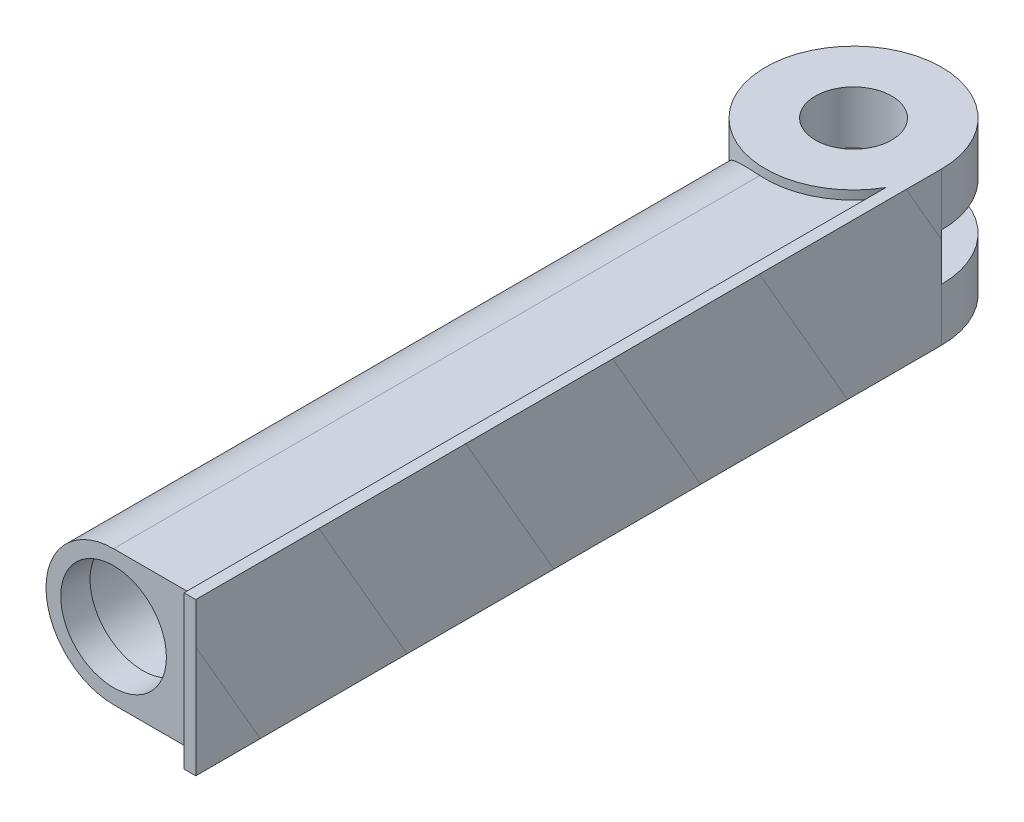
SolidWorks part; units mm, degrees
ref_plane "Front Plane" through (0, 0, 0) normal (0, 0, 1) x (1, 0, 0)
ref_plane "Top Plane" through (0, 0, 0) normal (0, 1, 0) x (1, 0, 0)
ref_plane "Right Plane" through (0, 0, 0) normal (1, 0, 0) x (0, 0, -1)
sketch "Sketch1" plane through (0, 0, 0) normal (0, 1, 0) x (1, 0, 0)
  circle A0 centre (0, 0) radius 30
  dimension "D1" = 60
extrude "Boss-Extrude1" add sketch "Sketch1" along normal mid plane 52
sketch "Sketch3" plane through (0, 0, 0) normal (0, 0, 1) x (1, 0, 0)
  line L1 (26, 23) -> (-2, 23)
  line L2 (30, 26) -> (30, -26)
  line L3 (26, -23) -> (-2, -23)
  line L4 (30, -26) -> (26, -26)
  line L7 (-30, -26) -> (30, -26) construction
  line L8 (26, -26) -> (26, -23)
  line L9 (30, 26) -> (26, 26)
  line L10 (30, 26) -> (-30, 26) construction
  line L11 (26, 26) -> (26, 23)
  arc A0 (-2, 23) -> (-2, -23) centre (-2, 0) ccw
  dimension "D4" = 28
  dimension "D1" = 4
  dimension "D2" = 3
  dimension "D3" = 3
  dimension "D5" = 4
extrude "Boss-Extrude2" add sketch "Sketch3" along normal blind 250 contours A0 | L1 L3 region at (4.945, 0, 0)
sketch "Sketch4" plane through (0, 0, 0) normal (0, 1, 0) x (1, 0, 0)
  circle A0 centre (0, 0) radius 13
  dimension "D1" = 26
extrude "Cut-Extrude2" cut sketch "Sketch4" against normal mid plane 52
extrude "Cut-Extrude3" cut sketch "Sketch1<2>" against normal blind 8
sketch "Sketch1<2>" plane through (0, 0, 0) normal (0, 1, 0) x (1, 0, 0) same geometry as "Sketch1"
extrude "Cut-Extrude4" cut sketch "Sketch1<3>" along normal blind 8
sketch "Sketch1<3>" plane through (0, 0, 0) normal (0, 1, 0) x (1, 0, 0) same geometry as "Sketch1"
sketch "Sketch5" plane through (0, 0, 250) normal (0, 0, 1) x (1, 0, 0)
  circle A0 centre (-2, 0) radius 19
  arc A2 (-2, 23) -> (-2, -23) centre (-2, 0) ccw construction
  dimension "D1" = 38
extrude "Cut-Extrude5" cut sketch "Sketch5" against normal blind 210
sketch "Sketch7" plane through (0, 0, 0) normal (0, 1, 0) x (1, 0, 0)
  line L0 (26, -250) -> (26, -254)
  line L1 (26, -254) -> (30, -254)
  line L2 (30, -254) -> (30, -250)
  line L3 (26, -250) -> (30, -250)
  dimension "D1" = 4
extrude "Boss-Extrude4" add sketch "Sketch7" along normal mid plane 52
sketch "Sketch8" plane through (30, 0, 0) normal (1, 0, 0) x (0, 0, -1)
  line L0 (-12.0631, 26) -> (0, 5.1061)
  line L2 (-62.0631, 26) -> (-32.0409, -26)
  line L3 (-112.0631, 26) -> (-82.0409, -26)
  line L4 (-162.0631, 26) -> (-132.0409, -26)
  line L5 (-212.0631, 26) -> (-182.0409, -26)
  line L6 (-254, 12.0343) -> (-232.0409, -26)
  line L8 (-254, 26) -> (0, 26)
  line L9 (-254, 26) -> (-254, -26)
  line L10 (-254, -26) -> (0, -26)
  line L11 (0, 26) -> (0, -26)
  dimension "D2" = 6
split line "Split Line1"
sketch "Sketch9" plane through (0, 0, 250) normal (0, 0, 1) x (1, 0, 0)
  circle A0 centre (-2, 0) radius 19
  circle A1 centre (-2, 0) radius 19 construction
  circle A2 centre (-2, 0) radius 18
  dimension "D1" = 36
extrude "Boss-Extrude5" add sketch "Sketch9" against normal blind 10
